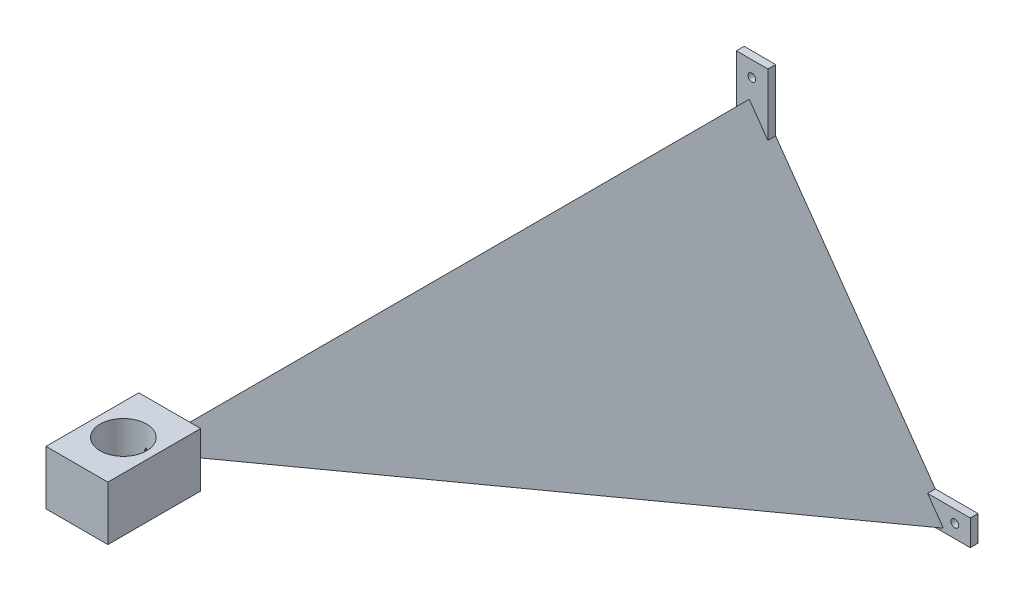
SolidWorks part; units mm, degrees
ref_plane "Plano frontal" through (0, 0, 0) normal (0, 0, 1) x (1, 0, 0)
ref_plane "Plano superior" through (0, 0, 0) normal (0, 1, 0) x (1, 0, 0)
ref_plane "Plano direito" through (0, 0, 0) normal (1, 0, 0) x (0, 0, -1)
sketch "Esboço2" plane through (0, 0, 0) normal (0, 0, 1) x (1, 0, 0)
  line L0 (-10.8631, 0) -> (204.1369, 0)
  line L1 (204.1369, 0) -> (77.102, 179.6166)
  line L2 (77.102, 179.6166) -> (-10.8631, 0)
  dimension "D1" = 215
  dimension "D2" = 220
  dimension "D3" = 200
ref_plane "Plano1" through (0, 0, 400) normal (0, 0, 1) x (1, 0, 0)
sketch "Esboço3" plane through (0, 0, 400) normal (0, 0, 1) x (1, 0, 0)
  point P0 (77.102, 179.6166)
loft "Loft1" add profiles "Esboço2", "Esboço3"
ref_plane "Plano3" through (77.102, 179.6166, 400) normal (0, 0, 1) x (1, 0, 0)
sketch "Esboço11" plane through (77.102, 179.6166, 400) normal (0, 0, 1) x (1, 0, 0)
  line L1 (20, -17.5) -> (-20, -17.5)
  line L2 (20, -17.5) -> (20, 17.5)
  line L3 (20, 17.5) -> (-20, 17.5)
  line L4 (-20, -17.5) -> (-20, 17.5)
  line L5 (20, -17.5) -> (-20, 17.5) construction
  line L6 (20, 17.5) -> (-20, -17.5) construction
  point P0 (0, 0)
  point P3 (0, 0)
  dimension "D1" = 35
  dimension "D2" = 40
extrude "Corte-extrusão2" cut sketch "Esboço11" against normal blind 20
sketch "Esboço12" plane through (0, 0, 380) normal (0, 0, 1) x (1, 0, 0)
  line L1 (57.5, 193) -> (97.5, 193)
  line L2 (57.5, 193) -> (57.5, 158)
  line L3 (57.5, 158) -> (97.5, 158)
  line L4 (97.5, 193) -> (97.5, 158)
  line L5 (57.5, 193) -> (97.5, 158) construction
  line L6 (57.5, 158) -> (97.5, 193) construction
  point P0 (77.5, 175.5)
  point P3 (77.5, 175.5)
  dimension "D1" = 35
  dimension "D2" = 40
extrude "Ressalto-extrusão2" add sketch "Esboço12" along normal blind 60
sketch "Esboço14" plane through (0, 193, 0) normal (0, 1, 0) x (1, 0, 0)
  line L0 (97.5, -440) -> (97.5, -380) construction
  line L1 (97.5, -440) -> (57.5, -440) construction
  circle A0 centre (77.5, -410) radius 15
  dimension "D1" = 30
  dimension "D2" = 20
  dimension "D3" = 30
extrude "Corte-extrusão3" cut sketch "Esboço14" against normal blind 30
sketch "Esboço16" plane through (0, 0, 0) normal (0, 0, -1) x (-1, 0, 0)
  line L1 (36.8444, -16.628) -> (-15.1182, -16.628)
  line L2 (36.8444, -16.628) -> (36.8444, 16.628)
  line L3 (36.8444, 16.628) -> (-15.1182, 16.628)
  line L4 (-15.1182, -16.628) -> (-15.1182, 16.628)
  line L5 (36.8444, -16.628) -> (-15.1182, 16.628) construction
  line L6 (36.8444, 16.628) -> (-15.1182, -16.628) construction
  point P0 (10.8631, 0)
extrude "Corte-extrusão5" cut sketch "Esboço16" against normal blind 5
sketch "Esboço17" plane through (0, 0, 5) normal (0, 0, -1) x (-1, 0, 0)
  line L0 (-15.1182, 0) -> (-15.1182, 16.628)
  line L1 (-15.1182, 0) -> (34.8818, 0)
  line L2 (-15.1182, 16.628) -> (34.8818, 16.628)
  line L3 (34.8818, 0) -> (34.8818, 16.628)
  dimension "D1" = 50
extrude "Ressalto-extrusão3" add sketch "Esboço17" along normal blind 5
sketch "Esboço18" plane through (0, 0, 0) normal (0, 0, -1) x (-1, 0, 0)
  line L1 (-238.3172, -16.628) -> (-169.9566, -16.628)
  line L2 (-238.3172, -16.628) -> (-238.3172, 16.628)
  line L3 (-238.3172, 16.628) -> (-169.9566, 16.628)
  line L4 (-169.9566, -16.628) -> (-169.9566, 16.628)
  line L5 (-238.3172, -16.628) -> (-169.9566, 16.628) construction
  line L6 (-238.3172, 16.628) -> (-169.9566, -16.628) construction
  point P0 (-204.1369, 0)
extrude "Corte-extrusão7" cut sketch "Esboço18" against normal blind 5
sketch "Esboço19" plane through (0, 0, 5) normal (0, 0, -1) x (-1, 0, 0)
  line L0 (-169.9566, 0) -> (-169.9566, 16.628)
  line L1 (-169.9566, 0) -> (-219.9566, 0)
  line L2 (-169.9566, 16.628) -> (-219.9566, 16.628)
  line L3 (-219.9566, 0) -> (-219.9566, 16.628)
  dimension "D1" = 50
extrude "Ressalto-extrusão4" add sketch "Esboço19" along normal blind 5
sketch "Esboço20" plane through (0, 0, 0) normal (0, 0, -1) x (-1, 0, 0)
  line L0 (-192.3766, 16.628) -> (-77.102, 179.6166) construction
  line L1 (-65.0658, 196.6348) -> (-89.1382, 196.6348)
  line L2 (-65.0658, 196.6348) -> (-65.0658, 162.5985)
  line L3 (-65.0658, 162.5985) -> (-89.1382, 162.5985)
  line L4 (-89.1382, 196.6348) -> (-89.1382, 162.5985)
  line L5 (-65.0658, 196.6348) -> (-89.1382, 162.5985) construction
  line L6 (-65.0658, 162.5985) -> (-89.1382, 196.6348) construction
  point P0 (-77.102, 179.6166)
extrude "Corte-extrusão8" cut sketch "Esboço20" against normal blind 5
sketch "Esboço21" plane through (0, 0, 5) normal (0, 0, -1) x (-1, 0, 0)
  line L0 (-68.7676, 162.5985) -> (-89.1382, 162.5985)
  line L1 (-68.7676, 162.5985) -> (-68.7676, 202.5985)
  line L2 (-89.1382, 162.5985) -> (-89.1382, 202.5985)
  line L3 (-68.7676, 202.5985) -> (-89.1382, 202.5985)
  dimension "D1" = 40
extrude "Ressalto-extrusão5" add sketch "Esboço21" along normal blind 5
sketch "Esboço22" plane through (0, 0, 5) normal (0, 0, 1) x (1, 0, 0)
  line L0 (219.9566, 16.628) -> (219.9566, 0) construction
  line L1 (192.3766, 16.628) -> (219.9566, 16.628) construction
  line L2 (-34.8818, 16.628) -> (-2.7197, 16.628) construction
  line L3 (-34.8818, 0) -> (-34.8818, 16.628) construction
  circle A0 centre (209.9566, 8.628) radius 2.5
  circle A1 centre (-24.8818, 8.628) radius 2.5
  dimension "D1" = 5
  dimension "D6" = 5
  dimension "D2" = 10
  dimension "D3" = 8
  dimension "D4" = 8
  dimension "D5" = 10
extrude "Corte-extrusão9" cut sketch "Esboço22" against normal blind 10
sketch "Esboço23" plane through (0, 0, 0) normal (0, 0, -1) x (-1, 0, 0)
  line L0 (-68.7676, 162.5985) -> (-68.7676, 202.5985) construction
  line L1 (-68.7676, 202.5985) -> (-89.1382, 202.5985) construction
  circle A0 centre (-78.7676, 192.5985) radius 2.5
  dimension "D2" = 5
  dimension "D1" = 10
  dimension "D3" = 10
extrude "Corte-extrusão10" cut sketch "Esboço23" against normal blind 10
sketch "Esboço26" plane through (0, 0, 0) normal (0, 0, -1) x (-1, 0, 0)
  line L0 (-188.2076, 2.5) -> (-3.7936, 2.5)
  line L1 (-15.1182, 0) -> (-169.9566, 0) construction
  line L2 (-189.845, 15.878) -> (-88.3734, 159.3504)
  line L3 (-192.3766, 16.628) -> (-89.1382, 162.5985) construction
  line L4 (-69.9734, 159.3765) -> (-0.471, 17.459)
  line L5 (-68.7676, 162.5985) -> (2.7197, 16.628) construction
  line L6 (-189.845, 15.878) -> (-188.2076, 2.5)
  line L7 (-0.471, 17.459) -> (-3.7936, 2.5)
  line L8 (-69.9734, 159.3765) -> (-88.3734, 159.3504)
  dimension "D1" = 2.5
  dimension "D2" = 2.5
  dimension "D3" = 2.5
loft "Loft de corte2" cut profiles "Esboço26", "Esboço3<3>"
sketch "Esboço3<3>" plane through (0, 0, 400) normal (0, 0, 1) x (1, 0, 0) same geometry as "Esboço3"
